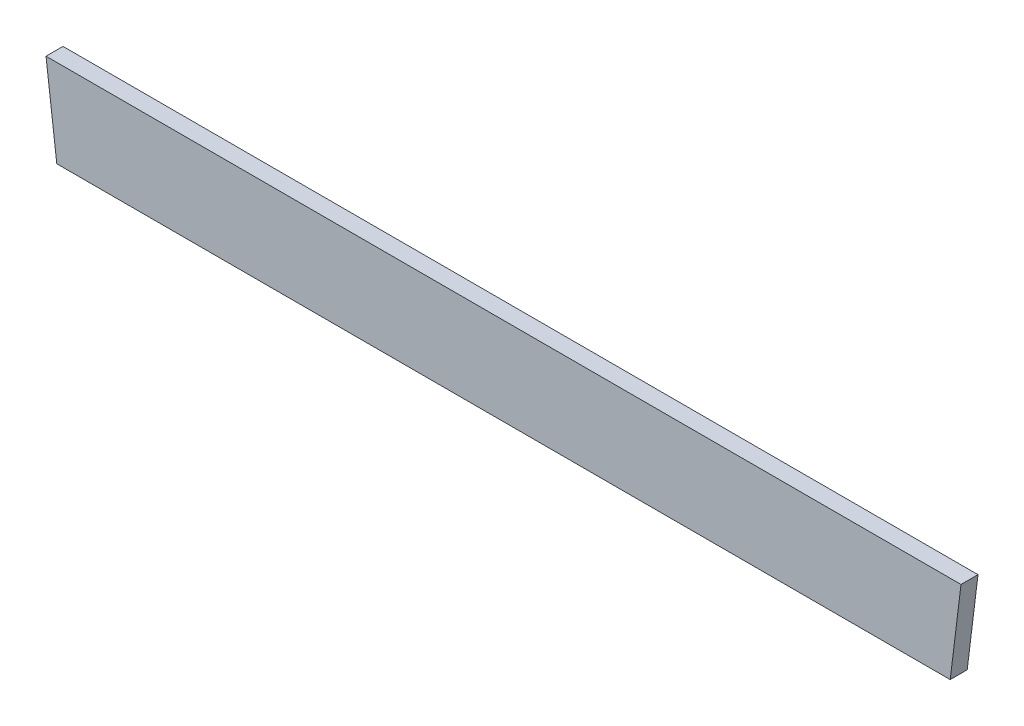
SolidWorks part; units mm, degrees
material "PC High Viscosity"
ref_plane "Front Plane" through (0, 0, 0) normal (0, 0, 1) x (1, 0, 0)
ref_plane "Top Plane" through (0, 0, 0) normal (0, 1, 0) x (1, 0, 0)
ref_plane "Right Plane" through (0, 0, 0) normal (1, 0, 0) x (0, 0, -1)
ref_axis "Axis1" through (0, -55, 0) along (0, 1, 0)
sketch "Sketch1" plane through (0, 0, 0) normal (0, 0, 1) x (1, 0, 0)
  line L2 (-269.1754, -62.6399) -> (-262.8323, -114.3)
  line L3 (269.1754, -62.6399) -> (262.8323, -114.3)
  line L5 (-262.8323, -114.3) -> (262.8323, -114.3)
  line L6 (269.1754, -62.6399) -> (-269.1754, -62.6399)
extrude "Boss-Extrude1" add sketch "Sketch1" along normal blind 10
